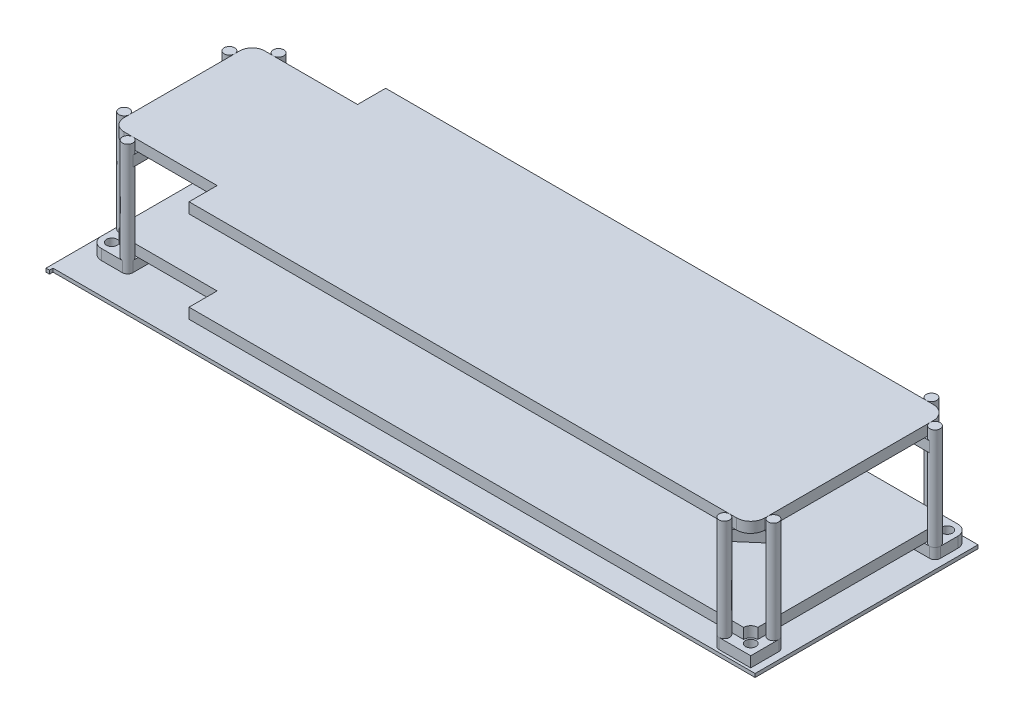
SolidWorks part; units mm, degrees
material "MDF"
ref_plane "Alzado" through (0, 0, 0) normal (0, 0, 1) x (1, 0, 0)
ref_plane "Planta" through (0, 0, 0) normal (0, 1, 0) x (1, 0, 0)
ref_plane "Vista lateral" through (0, 0, 0) normal (1, 0, 0) x (0, 0, -1)
sketch "Croquis1" plane through (0, 0, 0) normal (0, 1, 0) x (1, 0, 0)
  line L1 (-100, -31.75) -> (100, -31.75)
  line L2 (-100, -31.75) -> (-100, 31.75)
  line L3 (-100, 31.75) -> (100, 31.75)
  line L4 (100, -31.75) -> (100, 31.75)
  line L5 (-100, -31.75) -> (100, 31.75) construction
  line L6 (-100, 31.75) -> (100, -31.75) construction
  point P0 (0, 0)
  dimension "D1" = 63.5
  dimension "D2" = 200
extrude "Saliente-Extruir1" add sketch "Croquis1" along normal mid plane 55
shell "Vaciado1" thickness 1 removed face at (0, 27.5, 0) outward yes
sketch "Croquis3" plane through (0, 27.5, 0) normal (0, 1, 0) x (1, 0, 0)
  line L0 (-100.0164, 24.1433) -> (-101, 32.75)
  line L3 (-100.0164, 24.1433) -> (-65, 24.1433)
  line L4 (-65, 31.75) -> (-65, 24.1433)
  line L5 (-101, 32.75) -> (-65, 31.75)
  line L6 (-36.3, 0) -> (36.3, 0) construction
  line L7 (-100.0164, -24.1433) -> (-101, -32.75)
  line L8 (-100.0164, -24.1433) -> (-65, -24.1433)
  line L9 (-65, -31.75) -> (-65, -24.1433)
  line L10 (-101, -32.75) -> (-65, -31.75)
extrude "Saliente-Extruir2" add sketch "Croquis3" along normal blind 10 separate body
sketch "Croquis2" plane through (0, -27.5, 0) normal (0, 1, 0) x (1, 0, 0)
  line L0 (-95, 0) -> (95, 0) construction
  line L1 (-95, 20) -> (-95, -20) construction
  line L2 (95, 28) -> (95, -28) construction
  circle A0 centre (-95, 20) radius 1.5
  circle A1 centre (-95, -20) radius 1.5
  circle A2 centre (95, -28) radius 1.5
  circle A3 centre (95, 28) radius 1.5
  point P4 (0, 0)
  point P6 (0, 0)
  point P8 (-95, 0)
  point P13 (95, 0)
  dimension "D3" = 3
  dimension "D4" = 28
  dimension "D5" = 3
  dimension "D1" = 190
  dimension "D2" = 20
extrude "Cortar-Extruir1" cut sketch "Croquis2" against normal through all
sketch "Croquis5" plane through (0, -27.5, 0) normal (0, 1, 0) x (1, 0, 0)
  line L0 (-95, 23) -> (-89, 23)
  line L1 (-98, 20) -> (-98, 15)
  line L2 (-89, 20) -> (-95, 15)
  line L3 (-101, 0) -> (0, 0) construction
  line L4 (-101, 32.75) -> (-101, -32.75) construction
  line L5 (-89, -20) -> (-95, -15)
  line L6 (-98, -20) -> (-98, -15)
  line L7 (-95, -23) -> (-89, -23)
  arc A0 (-98, 20) -> (-95, 23) centre (-95, 20) cw
  arc A1 (-98, 15) -> (-95, 15) centre (-96.5, 15) ccw
  arc A2 (-89, 20) -> (-89, 23) centre (-89, 21.5) ccw
  circle A3 centre (-95, 20) radius 1.5
  circle A4 centre (-95, -20) radius 1.5
  arc A5 (-89, -20) -> (-89, -23) centre (-89, -21.5) cw
  arc A6 (-98, -15) -> (-95, -15) centre (-96.5, -15) cw
  arc A7 (-98, -20) -> (-95, -23) centre (-95, -20) ccw
  dimension "D1" = 3
  dimension "D2" = 6
  dimension "D4" = 1.5
  dimension "D3" = 5
  dimension "D5" = 1.5
  dimension "D6" = 3
extrude "Saliente-Extruir3" add sketch "Croquis5" along normal blind 3 separate body
sketch "Croquis6" plane through (0, -24.5, 0) normal (0, 1, 0) x (1, 0, 0)
  line L0 (-100, 0) -> (-89, 0) construction
  line L1 (-100, 31.75) -> (-100, -31.75) construction
  circle A0 centre (-96.5, 15) radius 1.5
  circle A1 centre (-89, 21.5) radius 1.5
  circle A2 centre (-96.5, -15) radius 1.5
  circle A3 centre (-89, -21.5) radius 1.5
  dimension "D1" = 3
  dimension "D2" = 8.4247
extrude "Saliente-Extruir5" add sketch "Croquis6" along normal blind 29 and the other way blind 3 separate body
combine bodies "Combinar1" operation type add bodies to combine 107 111 112
combine bodies "Combinar2" operation type add bodies to combine 106 110 109
ref_plane "Plano1" through (0, -1.5, 0) normal (0, 1, 0) x (1, 0, 0)
sketch "Croquis7" plane through (0, -1.5, 0) normal (0, 1, 0) x (1, 0, 0)
  line L0 (-96.5, 13.5) -> (-89.5, 13.5)
  line L1 (-87.5, 15.5) -> (-87.5, 21.5)
  line L2 (-87.5, 21.5) -> (-89, 21.5)
  line L3 (-89, 21.5) -> (-96.5, 15)
  line L4 (-96.5, 15) -> (-96.5, 13.5)
  line L5 (-101, 0) -> (0, 0) construction
  line L6 (-101, 32.75) -> (-101, -32.75) construction
  line L7 (-89, -21.5) -> (-96.5, -15)
  line L8 (-87.5, -21.5) -> (-89, -21.5)
  line L9 (-87.5, -15.5) -> (-87.5, -21.5)
  line L10 (-96.5, -13.5) -> (-89.5, -13.5)
  line L11 (-96.5, -15) -> (-96.5, -13.5)
  circle A1 centre (-96.5, 15) radius 1.5 construction
  circle A2 centre (-89, 21.5) radius 1.5 construction
  arc A3 (-89.5, 13.5) -> (-87.5, 15.5) centre (-89.5, 15.5) ccw
  arc A4 (-89.5, -13.5) -> (-87.5, -15.5) centre (-89.5, -15.5) cw
  dimension "D1" = 2
extrude "Saliente-Extruir6" add sketch "Croquis7" along normal blind 3 separate body
combine bodies "Combinar3" operation type add bodies to combine 116 113
sketch "Croquis8" plane through (-101, 0, 0) normal (-1, 0, 0) x (0, 0, 1)
  line L1 (-32.75, -27.5) -> (32.75, -27.5)
  line L2 (-32.75, -27.5) -> (-32.75, 27.5)
  line L3 (-32.75, 27.5) -> (32.75, 27.5)
  line L4 (32.75, -27.5) -> (32.75, 27.5)
  line L5 (-32.75, -27.5) -> (32.75, 27.5) construction
  line L6 (-32.75, 27.5) -> (32.75, -27.5) construction
  point P0 (0, 0)
extrude "Cortar-Extruir2" cut sketch "Croquis8" against normal blind 1
combine bodies "Combinar4" operation type add bodies to combine 114 115
sketch "Croquis9" plane through (0, -24.5, 0) normal (0, 1, 0) x (1, 0, 0)
  line L3 (0, 0) -> (-100, 0) construction
  line L4 (-96.5, -13.5) -> (-89.5, -13.5)
  line L5 (-87.5, -15.5) -> (-87.5, -21.5)
  line L6 (-96.5, 13.5) -> (-89.5, 13.5)
  line L7 (-87.5, 15.5) -> (-87.5, 21.5)
  line L8 (-90.1335, 20.5176) -> (-95.3665, 15.9824)
  line L9 (-96.5, 13.5) -> (-89.5, 13.5)
  line L10 (-87.5, 15.5) -> (-87.5, 21.5)
  line L11 (-90.1335, 20.5176) -> (-95.3665, 15.9824)
  line L12 (-90.1335, -20.5176) -> (-95.3665, -15.9824)
  arc A3 (-89.5, -13.5) -> (-87.5, -15.5) centre (-89.5, -15.5) cw
  arc A4 (-90.1335, -20.5176) -> (-87.5, -21.5) centre (-89, -21.5) cw
  arc A5 (-96.5, -13.5) -> (-95.3665, -15.9824) centre (-96.5, -15) cw
  arc A6 (-96.5, 13.5) -> (-95.3665, 15.9824) centre (-96.5, 15) ccw
  arc A7 (-89.5, 13.5) -> (-87.5, 15.5) centre (-89.5, 15.5) ccw
  arc A8 (-90.1335, 20.5176) -> (-87.5, 21.5) centre (-89, 21.5) ccw
  arc A9 (-96.5, 13.5) -> (-95.3665, 15.9824) centre (-96.5, 15) ccw
  arc A10 (-89.5, 13.5) -> (-87.5, 15.5) centre (-89.5, 15.5) ccw
  arc A11 (-90.1335, 20.5176) -> (-87.5, 21.5) centre (-89, 21.5) ccw
  dimension "D2" = 100
  dimension "D1" = 0
extrude "Saliente-Extruir7" add sketch "Croquis9" against normal up to surface (3 mm away) separate body up to face at (95, -27.5, -29.5)
combine bodies "Combinar5" operation type add bodies to combine 121 119
combine bodies "Combinar7" operation type add bodies to combine 117 120
sketch "Croquis10" plane through (0, 1.5, 0) normal (0, 1, 0) x (1, 0, 0)
  line L1 (-95, 20) -> (95, 20)
  line L2 (-95, 20) -> (-95, -20)
  line L3 (-95, -20) -> (95, -20)
  line L4 (95, 20) -> (95, -20)
extrude "Saliente-Extruir9" add sketch "Croquis10" along normal blind 3 separate body
sketch "Croquis11" plane through (0, 4.5, 0) normal (0, 1, 0) x (1, 0, 0)
  line L1 (95, 28) -> (-65, 28)
  line L2 (95, 28) -> (95, -28)
  line L3 (95, -28) -> (-65, -28)
  line L4 (-65, 28) -> (-65, -28)
  dimension "D1" = 56
  dimension "D2" = 160
extrude "Saliente-Extruir10" add sketch "Croquis11" against normal blind 3 separate body
combine bodies "Combinar8" operation type add bodies to combine 125 124
pattern_linear "MatrizL2" count 2 spacing 26 along (0, -1, 0) of "Saliente-Extruir10", "Saliente-Extruir9"
combine bodies "Combinar9" operation type add bodies to combine 128 129
sketch "Croquis12" plane through (0, 4.5, 0) normal (0, 1, 0) x (1, 0, 0)
  line L0 (-95, 20) -> (-95, 16.5)
  line L1 (-95, 20) -> (-95, -20) construction
  line L2 (-95, 20) -> (-91.5, 20)
  line L3 (-65, 20) -> (-95, 20) construction
  line L4 (-101, 0) -> (0, 0) construction
  line L5 (-101, 32.75) -> (-101, -32.75) construction
  line L6 (-95, -20) -> (-91.5, -20)
  line L7 (-95, -20) -> (-95, -16.5)
  arc A0 (-91.5, 20) -> (-95, 16.5) centre (-91.5, 16.5) ccw
  arc A1 (-91.5, -20) -> (-95, -16.5) centre (-91.5, -16.5) cw
  dimension "D1" = 3.5
extrude "Cortar-Extruir3" cut sketch "Croquis12" against normal up to surface (29 mm away) up to face at (-92.6509, -24.5, 18.1509)
sketch "Croquis13" plane through (101, 0, 0) normal (1, 0, 0) x (0, 0, -1)
  line L1 (-32.75, 27.5) -> (32.75, 27.5)
  line L2 (-32.75, 27.5) -> (-32.75, -28.5)
  line L3 (-32.75, -28.5) -> (32.75, -28.5)
  line L4 (32.75, 27.5) -> (32.75, -28.5)
extrude "Cortar-Extruir4" cut sketch "Croquis13" against normal blind 1
sketch "Croquis14" plane through (0, 4.5, 0) normal (0, 1, 0) x (1, 0, 0)
  line L0 (95, 0) -> (73.119, 0) construction
  line L1 (95, -28) -> (95, 28) construction
  circle A0 centre (95, 28) radius 1.5
  circle A1 centre (95, -28) radius 1.5
extrude "Cortar-Extruir5" cut sketch "Croquis14" against normal blind 60
ref_plane "Plano2" through (0, -27.5, 0) normal (0, -1, 0) x (-1, 0, 0)
sketch "Croquis16" plane through (0, -27.5, 0) normal (0, -1, 0) x (-1, 0, 0)
  line L1 (-98, 31) -> (-89, 31)
  line L2 (-98, 31) -> (-98, 23)
  line L3 (-96.5, 21.5) -> (-87.5, 21.5)
  line L4 (-87.5, 29.5) -> (-87.5, 21.5)
  circle A0 centre (-95, 28) radius 1.5 construction
  arc A1 (-98, 23) -> (-96.5, 21.5) centre (-96.5, 23) ccw
  arc A2 (-87.5, 29.5) -> (-89, 31) centre (-89, 29.5) ccw
  dimension "D1" = 3
  dimension "D2" = 3
  dimension "D5" = 3
  dimension "D6" = 3
  dimension "D7" = 1.5
  dimension "D8" = 1.5
  dimension "D9" = 1.5
  dimension "D10" = 1.5
  dimension "D3" = 9.5
  dimension "D4" = 10.5
extrude "Saliente-Extruir11" add sketch "Croquis16" against normal blind 3
fillet "Redondeo1" radius 3 1 edges at (98, -26, -31)
sketch "Croquis19" plane through (0, -24.5, 0) normal (0, 1, 0) x (1, 0, 0)
  circle A0 centre (96.5, 23) radius 1.495
  circle A1 centre (89, 29.5) radius 1.495
  dimension "D1" = 2.99
  dimension "D2" = 2.99
extrude "Saliente-Extruir14" add sketch "Croquis19" along normal blind 29
sketch "Croquis20" plane through (0, -24.5, 0) normal (0, 1, 0) x (1, 0, 0)
  circle A0 centre (95, 28) radius 1.5
  dimension "D1" = 3
extrude "Cortar-Extruir6" cut sketch "Croquis20" against normal blind 50
sketch "Croquis21" plane through (0, -21.5, 0) normal (0, 1, 0) x (1, 0, 0)
  line L0 (-36.3, 0) -> (36.3, 0) construction
  circle A0 centre (95.0001, 27.9765) radius 2
  circle A1 centre (95.0001, -27.9765) radius 2
  dimension "D1" = 4
extrude "Cortar-Extruir7" cut sketch "Croquis21" against normal blind 3
sketch "Croquis22" plane through (0, 4.5, 0) normal (0, 1, 0) x (1, 0, 0)
  line L0 (93.5, 28) -> (95, 28)
  line L1 (95, 28) -> (95, 26.5)
  line L2 (-36.3, 0) -> (36.3, 0) construction
  line L3 (93.5, -28) -> (95, -28)
  line L4 (95, -28) -> (95, -26.5)
  arc A0 (93.5, 28) -> (95, 26.5) centre (95, 28) ccw
  arc A1 (93.5, -28) -> (95, -26.5) centre (95, -28) cw
  dimension "D1" = 3
extrude "Saliente-Extruir15" add sketch "Croquis22" against normal blind 3
mirror "Simetría1" about plane through (0, 0, 0) normal (0, 0, 1) of "Saliente-Extruir11"
sketch "Croquis23" plane through (0, -24.5, 0) normal (0, 1, 0) x (1, 0, 0)
  line L0 (95, -28) -> (95, 28) construction
  circle A0 centre (95, -28) radius 1.5
  dimension "D1" = 3
extrude "Cortar-Extruir8" cut sketch "Croquis23" against normal blind 4
mirror "Simetría2" about plane through (0, 0, 0) normal (0, 0, 1) of "Saliente-Extruir14"
fillet "Redondeo4" radius 3 1 edges at (87.5, -26, -21.5)
fillet "Redondeo5" radius 3 1 edges at (87.5, -26, 21.5)
sketch "Croquis26" plane through (0, 0, 0) normal (0, 1, 0) x (1, 0, 0)
  line L2 (89, 29.5) -> (96.5, 23)
  line L3 (89, 29.5) -> (87.5, 29.5)
  line L4 (96.5, 23) -> (96.5, 21.5)
  line L5 (87.5, 29.5) -> (87.5, 21.5)
  line L6 (87.5, 21.5) -> (96.5, 21.5)
  circle A0 centre (89, 29.5) radius 1.5
  circle A1 centre (96.5, 23) radius 1.5
  dimension "D1" = 8
extrude "Saliente-Extruir16" add sketch "Croquis26" along normal mid plane 3 contours A1 L2 A0 L5 L6 region at (90.8298, 0, -24.4046)
fillet "Redondeo6" radius 3 1 edges at (87.5, 0, -21.5)
mirror "Simetría3" about plane through (0, 0, 0) normal (0, 0, 1) of "Saliente-Extruir16"
fillet "Redondeo7" radius 3 1 edges at (87.5, 0, 21.5)
fillet "Redondeo8" radius 4 1 edges at (95, 3, -28)
fillet "Redondeo9" radius 4 1 edges at (95, 3, 28)
ref_plane "Plano3" through (0, 0, 31.75) normal (0, 0, 1) x (1, 0, 0)
sketch "Croquis28" plane through (0, 0, 31.75) normal (0, 0, 1) x (1, 0, 0)
  line L1 (-100, 27.5) -> (100, 27.5)
  line L2 (-100, 27.5) -> (-100, -28.5)
  line L3 (-100, -28.5) -> (100, -28.5)
  line L4 (100, 27.5) -> (100, -28.5)
extrude "Cortar-Extruir9" cut sketch "Croquis28" along normal blind 20
ref_plane "Plano4" through (0, 0, -31.75) normal (0, 0, -1) x (-1, 0, 0)
sketch "Croquis29" plane through (0, 0, -31.75) normal (0, 0, -1) x (-1, 0, 0)
  line L1 (-100, 27.5) -> (100, 27.5)
  line L2 (-100, 27.5) -> (-100, -28.5)
  line L3 (-100, -28.5) -> (100, -28.5)
  line L4 (100, 27.5) -> (100, -28.5)
extrude "Cortar-Extruir10" cut sketch "Croquis29" along normal blind 10
sketch "Croquis30" plane through (0.8311, 0, -29.9214) normal (0.0278, 0, -0.9996) x (-0.9996, 0, -0.0278)
  line L1 (46.7932, 21.8591) -> (118.945, 21.8591)
  line L2 (46.7932, 21.8591) -> (46.7932, 44.5354)
  line L3 (46.7932, 44.5354) -> (118.945, 44.5354)
  line L4 (118.945, 21.8591) -> (118.945, 44.5354)
  line L5 (46.7932, 21.8591) -> (118.945, 44.5354) construction
  line L6 (46.7932, 44.5354) -> (118.945, 21.8591) construction
  point P0 (82.8691, 33.1972)
extrude "Cortar-Extruir11" cut sketch "Croquis30" against normal blind 100
fillet "Redondeo3" radius 3 rebuild error yes
